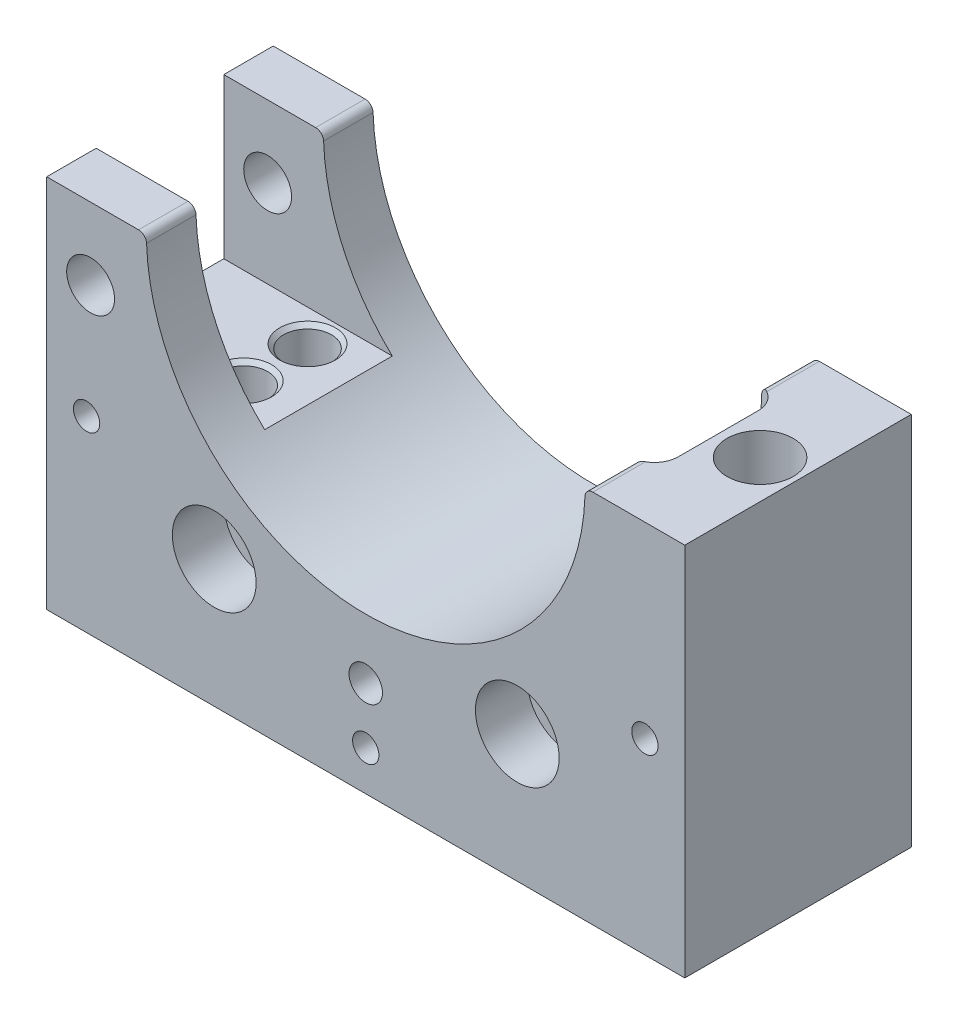
SolidWorks part; units mm, degrees
ref_plane "前视基准面" through (0, 0, 0) normal (0, 0, 1) x (1, 0, 0)
ref_plane "上视基准面" through (0, 0, 0) normal (0, 1, 0) x (1, 0, 0)
ref_plane "右视基准面" through (0, 0, 0) normal (1, 0, 0) x (0, 0, -1)
sketch "草图1" plane through (0, 0, 0) normal (0, 0, 1) x (1, 0, 0)
  line L0 (27.5, 23.5) -> (40, 23.5)
  line L1 (-40, 23.5) -> (-27.5, 23.5)
  line L2 (-40, 23.5) -> (-40, -23.5)
  line L3 (-40, -23.5) -> (40, -23.5)
  line L4 (40, 23.5) -> (40, -23.5)
  line L5 (-40, 23.5) -> (40, -23.5) construction
  line L6 (-40, -23.5) -> (40, 23.5) construction
  arc A0 (-27.5, 23.5) -> (27.5, 23.5) centre (0, 23.5) ccw
  point P0 (0, 0)
  dimension "D3" = 55
  dimension "D1" = 80
  dimension "D2" = 47
extrude "凸台-拉伸1" add sketch "草图1" along normal blind 28.4
sketch "草图2" plane through (0, 23.5, 0) normal (0, 1, 0) x (1, 0, 0)
  line L1 (-110, -6.2) -> (30, -6.2)
  line L2 (-110, -6.2) -> (-110, -22.2)
  line L3 (-110, -22.2) -> (30, -22.2)
  line L4 (30, -6.2) -> (30, -22.2)
  line L5 (-110, -6.2) -> (30, -22.2) construction
  line L6 (-110, -22.2) -> (30, -6.2) construction
  line L8 (-27.5, 0) -> (-40, 0) construction
  point P0 (-40, -14.2)
  dimension "D1" = 16
  dimension "D2" = 70
  dimension "D3" = 14.2
extrude "切除-拉伸1" cut sketch "草图2" against normal blind 20
fillet "圆角1" radius 3 2 edges at (30, 13.5, 22.2) (30, 13.5, 6.2)
sketch "草图3" plane through (0, 3.5, 0) normal (0, 1, 0) x (1, 0, 0)
  line L0 (-18.8746, -14.2) -> (-40, -14.2) construction
  line L1 (-18.8746, -22.2) -> (-18.8746, -6.2) construction
  line L2 (-40, -6.2) -> (-40, -22.2) construction
  line L3 (-18.8746, -14.2) -> (18.8746, -14.2) construction
  line L4 (18.8746, -6.2) -> (18.8746, -22.2) construction
  line L5 (0, -7.5816) -> (0, -21.1916) construction
  circle A0 centre (-25.5, -10.2) radius 3
  circle A1 centre (-25.5, -18.2) radius 3
  circle A2 centre (25.5, -10.2) radius 3.05
  circle A3 centre (25.5, -18.2) radius 3.05
  dimension "D1" = 6
  dimension "D2" = 8
  dimension "D3" = 6.1
  dimension "D4" = 51
  dimension "D5" = 25.5
extrude "切除-拉伸2" cut sketch "草图3" against normal through all
chamfer "倒角1" distance 0.5 angle 45 4 edges at (-25.5, 3.5, 15.2) (-25.5, 3.5, 13.2) (25.5, 3.5, 15.15) (25.5, 3.5, 13.25)
sketch "草图4" plane through (0, 0, 28.4) normal (0, 0, 1) x (1, 0, 0)
  circle A0 centre (-34.4994, 14.4751) radius 3
  dimension "D1" = 6
extrude "切除-拉伸3" cut sketch "草图4" against normal through all
sketch "草图7" plane through (0, 23.5, 0) normal (0, 1, 0) x (1, 0, 0)
  line L0 (40, -14.2) -> (30, -14.2) construction
  line L1 (40, -28.4) -> (40, 0) construction
  line L2 (30, -19.2) -> (30, -9.2) construction
  circle A0 centre (35.2, -14.155) radius 4.15
  dimension "D1" = 8.3
  dimension "D2" = 4.8
extrude "切除-拉伸4" cut sketch "草图7" against normal blind 18
hole_wizard "M6 螺纹孔2" positions "草图9" profile "草图8" tap size "M6" standard "Gb" end condition through all
sketch "草图9" plane through (0, 5.5, 0) normal (0, 1, 0) x (1, 0, 0)
  point P0 (35.2, -14.155)
cosmetic thread "孔螺蚊线2" parameters "D2"=6
sketch "草图8" plane through (35.2, 5.5, 14.155) normal (1, 0, 0) x (0, 0, 1)
  line L0 (0, 0) -> (0, 29)
  line L1 (0, 29) -> (2.5, 29)
  line L2 (2.5, 29) -> (2.5, 0)
  line L5 (2.5, 0) -> (0, 0)
  line L11 (0, -6.35) -> (0, 107.95) construction
  dimension "通孔螺纹孔钻头直径" = 5
  dimension "通孔螺纹孔钻头深度" = 29
sketch "草图10" plane through (0, 0, 28.4) normal (0, 0, 1) x (1, 0, 0)
  line L0 (0, -4) -> (0, -23.5) construction
  line L1 (-40, -23.5) -> (40, -23.5) construction
  circle A0 centre (-19, -7.5) radius 3.1
  arc A1 (-27.5, 23.5) -> (27.5, 23.5) centre (0, 23.5) ccw construction
  circle A2 centre (19, -7.5) radius 3.1
  dimension "D1" = 6.2
  dimension "D2" = 16
  dimension "D3" = 38
extrude "切除-拉伸5" cut sketch "草图10" against normal through all
ref_plane "基准面1" through (0, 0, 14.2) normal (0, 0, 1) x (1, 0, 0)
hole_wizard "M5 螺纹孔1" positions "草图14" profile "草图12" tap size "M5" standard "Gb"
sketch "草图14" plane through (0, 0, 28.4) normal (0, 0, 1) x (1, 0, 0)
  line L0 (0, -4) -> (0, -23.5) construction
  line L1 (-40, -23.5) -> (40, -23.5) construction
  arc A0 (-27.5, 23.5) -> (27.5, 23.5) centre (0, 23.5) ccw construction
  point P12 (0, -11.5)
  dimension "D1" = 12
sketch "草图12" plane through (0, -11.5, 28.4) normal (1, 0, 0) x (0, -1, 0)
  line L0 (0, 0) -> (0, 15.6618)
  line L1 (0, 15.6618) -> (2.1, 14.4)
  line L2 (2.1, 14.4) -> (2.1, 0)
  line L5 (2.1, 0) -> (0, 0)
  line L10 (0, 15.6618) -> (-2.1, 14.4) construction
  line L11 (0, -6.35) -> (0, 107.95) construction
  dimension "螺纹孔钻头直径" = 4.2
  dimension "螺纹孔钻头深度" = 14.4
  dimension "导头角度" = 118
cosmetic thread "孔螺蚊线3" parameters "D1"=12, "D2"=5
hole_wizard "M5 螺纹孔2" positions "草图16" profile "草图15" tap size "M5" standard "Gb"
sketch "草图16" plane through (0, 0, 0) normal (0, 0, -1) x (-1, 0, 0)
  point P0 (0, -11.5)
sketch "草图15" plane through (0, -11.5, 0) normal (1, 0, 0) x (0, 1, 0)
  line L0 (0, 0) -> (0, 15.6618)
  line L1 (0, 15.6618) -> (2.1, 14.4)
  line L2 (2.1, 14.4) -> (2.1, 0)
  line L5 (2.1, 0) -> (0, 0)
  line L10 (0, 15.6618) -> (-2.1, 14.4) construction
  line L11 (0, -6.35) -> (0, 107.95) construction
  dimension "螺纹孔钻头直径" = 4.2
  dimension "螺纹孔钻头深度" = 14.4
  dimension "导头角度" = 118
cosmetic thread "孔螺蚊线4" parameters "D1"=12, "D2"=5
fillet "圆角2" radius 1 4 edges at (27.5, 23.5, 25.279) (27.5, 23.5, 3.121) (-27.5, 23.5, 25.3) (-27.5, 23.5, 3.1)
sketch "草图17" plane through (0, 0, 0) normal (0, 0, -1) x (-1, 0, 0)
  circle A0 centre (-19, -7.5) radius 5.25
  circle A1 centre (19, -7.5) radius 5.25
  dimension "D1" = 10.5
extrude "切除-拉伸7" cut sketch "草图17" against normal blind 6.5
mirror "镜向3" about plane through (0, 0, 14.2) normal (0, 0, 1) of "切除-拉伸7"
hole_wizard "M4 螺纹孔1" positions "草图19" profile "草图18" tap size "M4" standard "Gb"
sketch "草图19" plane through (0, 0, 28.4) normal (0, 0, 1) x (1, 0, 0)
  line L0 (0, -23.5) -> (0, -4) construction
  line L1 (-40, -23.5) -> (40, -23.5) construction
  line L4 (-40, 0) -> (40, 0) construction
  line L5 (-40, 23.5) -> (-40, -23.5) construction
  line L6 (40, -23.5) -> (40, 23.5) construction
  arc A0 (-27.4831, 22.5351) -> (27.4831, 22.5351) centre (0, 23.5) ccw construction
  point P21 (-35, 0)
  point P23 (35, 0)
  point P27 (0, -18.5)
  dimension "D1" = 70
  dimension "D2" = 23.5
  dimension "D3" = 5
sketch "草图18" plane through (-35, 0, 28.4) normal (1, 0, 0) x (0, -1, 0)
  line L0 (0, 0) -> (0, 10.9914)
  line L1 (0, 10.9914) -> (1.65, 10)
  line L2 (1.65, 10) -> (1.65, 0)
  line L5 (1.65, 0) -> (0, 0)
  line L10 (0, 10.9914) -> (-1.65, 10) construction
  line L11 (0, -6.35) -> (0, 107.95) construction
  dimension "螺纹孔钻头直径" = 3.3
  dimension "螺纹孔钻头深度" = 10
  dimension "导头角度" = 118
cosmetic thread "孔螺蚊线5" parameters "D1"=8, "D2"=4
cosmetic thread "孔螺蚊线6" parameters "D1"=8, "D2"=4
cosmetic thread "孔螺蚊线7" parameters "D1"=8, "D2"=4
mirror "镜向4" about plane through (0, 0, 14.2) normal (0, 0, 1) of "M4 螺纹孔1"
